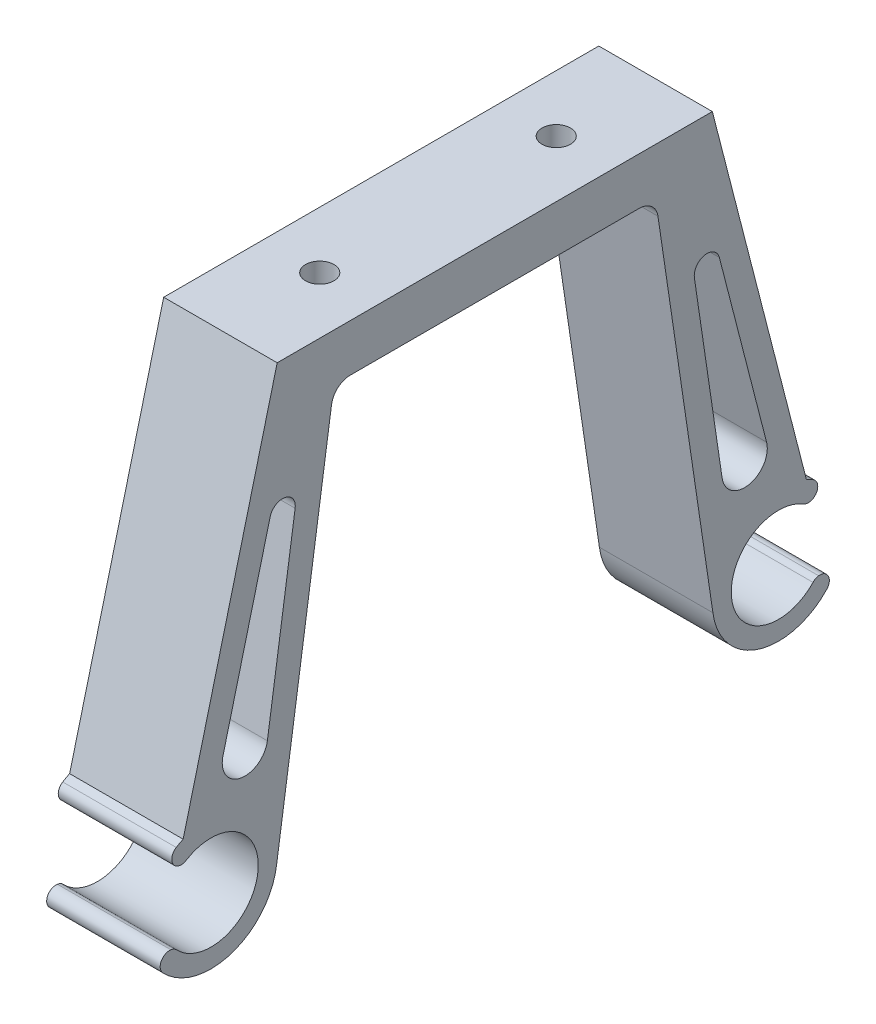
SolidWorks part; units mm, degrees
ref_plane "Front Plane" through (0, 0, 0) normal (0, 0, 1) x (1, 0, 0)
ref_plane "Top Plane" through (0, 0, 0) normal (0, 1, 0) x (1, 0, 0)
ref_plane "Right Plane" through (0, 0, 0) normal (1, 0, 0) x (0, 0, -1)
sketch "Sketch1" plane through (0, 0, 0) normal (1, 0, 0) x (0, 0, -1)
  circle A0 centre (-30, 0) radius 7
  circle A2 centre (-30, 0) radius 5
extrude "Boss-Extrude1" add sketch "Sketch1" along normal blind 12
sketch "Sketch3" plane through (12, 0, 0) normal (1, 0, 0) x (0, 0, -1)
  line L0 (-26.1324, 3.1689) -> (-27.0925, -4.0677)
  line L1 (-26.1324, 3.1689) -> (-39.5877, 4.9539)
  line L2 (-27.0925, -4.0677) -> (-40.5478, -2.2826)
  line L3 (-39.5877, 4.9539) -> (-40.5478, -2.2826)
  line L4 (-36.998, 0.1689) -> (36.8676, 0.1689) construction
  circle A0 centre (-30, 0) radius 5 construction
  circle A1 centre (-30, 0) radius 7 construction
  dimension "D1" = 7.3
  dimension "D2" = 3
extrude "Cut-Extrude1" cut sketch "Sketch3" against normal through all
fillet "Fillet1" radius 1 4 edges at (6, 4.0677, 32.9075) (6, 4.4038, 35.4412) (6, -3.1689, 33.8676) (6, -2.8328, 36.4012)
sketch "Sketch4" plane through (12, 0, 0) normal (1, 0, 0) x (0, 0, -1)
  line L0 (-23.0608, -0.9206) -> (-17, 40)
  line L1 (-17, 40) -> (0, 40)
  line L2 (0, 40) -> (0, 45)
  line L3 (0, 45) -> (-23, 45)
  line L4 (-23, 45) -> (-32.941, 6.3522)
  line L5 (-30, 0) -> (0, 0) construction
  arc A0 (-35.0988, -4.7961) -> (-33.6718, 5.9597) centre (-30, 0) ccw construction
  arc A7 (-33.6718, 5.9597) -> (-33.2788, 4.117) centre (-33.1473, 5.1083) ccw
  arc A8 (-33.2788, 4.117) -> (-32.6227, 4.2569) centre (-33.1473, 5.1083) ccw
  arc A9 (-33.642, -3.4258) -> (-32.6227, 4.2569) centre (-30, 0) ccw
  arc A10 (-33.642, -3.4258) -> (-34.2389, -3.1196) centre (-34.3704, -4.1109) ccw
  arc A11 (-34.2389, -3.1196) -> (-35.0988, -4.7961) centre (-34.3704, -4.1109) ccw
  arc A12 (-35.0988, -4.7961) -> (-33.6718, 5.9597) centre (-30, 0) ccw
  arc A18 (-23.0608, -0.9206) -> (-32.941, 6.3522) centre (-30, 0) ccw
  dimension "D1" = 17
  dimension "D2" = 23
  dimension "D3" = 5
  dimension "D4" = 40
  dimension "D5" = 6
  dimension "D6" = 0
extrude "Boss-Extrude2" add sketch "Sketch4" against normal up to surface (12 mm away) up to face at (0, 0.096, 30.7237)
fillet "Fillet2" radius 2 1 edges at (6, 40, 17)
sketch "Sketch6" plane through (12, 0, 0) normal (1, 0, 0) x (0, 0, -1)
  line L0 (-17.3284, 56.211) -> (-30.7804, 3.9133)
  line L1 (-30.7804, 3.9133) -> (-25.3866, 1.8045)
  line L2 (-25.3866, 1.8045) -> (-17.3284, 56.211)
  line L3 (-23.0608, -0.9206) -> (-17.2528, 38.293) construction
  line L4 (-23, 45) -> (-32.941, 6.3522) construction
  circle A0 centre (-27.5644, 5.5598) radius 2.7045
  circle A1 centre (-22.438, 30.9272) radius 1.35
  circle A2 centre (-26.412, 11.2621) radius 2.4
  dimension "D1" = 54
  dimension "D3" = 55
  dimension "D5" = 2.7
  dimension "D2" = 2.7
  dimension "D4" = 2.7
extrude "Cut-Extrude2" cut sketch "Sketch6" against normal through all contours A2 L2 A1 L0 | A2 | A1 region at (12, 20.8464, 24.4752) region at (12, 11.2621, 26.412)
mirror "Mirror9" about plane through (-56.5138, 40, 0) normal (0, 0, -1) of bodies 105
sketch "Sketch7" plane through (0, 45, 0) normal (0, 1, 0) x (1, 0, 0)
  line L0 (0, -23) -> (0, 23) construction
  circle A0 centre (6, -12.5) radius 1.5
  circle A1 centre (6, 12.5) radius 1.5
  point P6 (0, 0)
  dimension "D5" = 3
  dimension "D6" = 3
  dimension "D1" = 6
  dimension "D2" = 6
  dimension "D3" = 12.5
  dimension "D4" = 12.5
extrude "Cut-Extrude3" cut sketch "Sketch7" against normal through all
